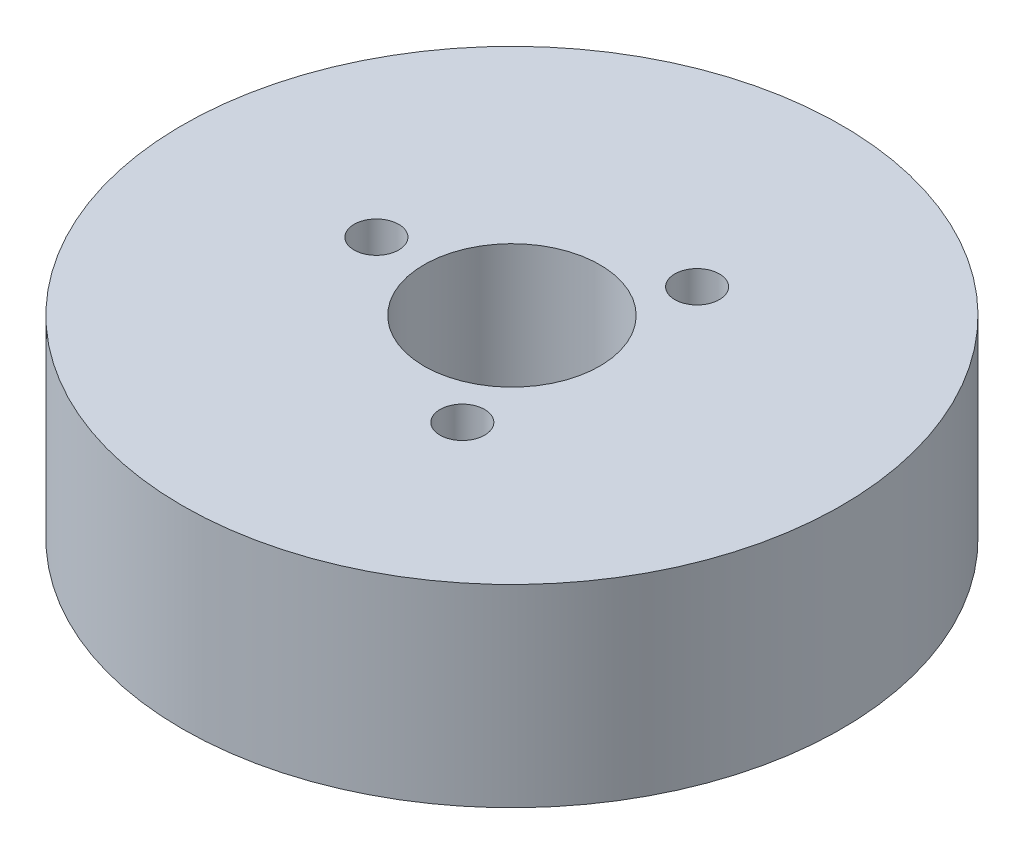
SolidWorks part; units mm, degrees
ref_plane "Front Plane" through (0, 0, 0) normal (0, 0, 1) x (1, 0, 0)
ref_plane "Top Plane" through (0, 0, 0) normal (0, 1, 0) x (1, 0, 0)
ref_plane "Right Plane" through (0, 0, 0) normal (1, 0, 0) x (0, 0, -1)
sketch "Sketch1" plane through (0, 0, 0) normal (0, 1, 0) x (1, 0, 0)
  circle A0 centre (0, 0) radius 37.5
  dimension "FLANGE_OD" = 75
extrude "Boss-Extrude1" add sketch "Sketch1" along normal blind 22
sketch "Sketch2" plane through (0, 0, 0) normal (0, 1, 0) x (1, 0, 0)
  circle A0 centre (0, 0) radius 10
  dimension "BORE_D" = 20
extrude "Cut-Extrude1" cut sketch "Sketch2" along normal through all
sketch "Sketch3" plane through (0, 22, 0) normal (0, 1, 0) x (1, 0, 0)
  circle A0 centre (0, 0) radius 15.4224 construction
  circle A1 centre (-15.4224, 0) radius 2.539
  dimension "BOLT_D" = 5.078
  dimension "BOLT_PCD" = 30.8448
extrude "Cut-Extrude2" cut sketch "Sketch3" against normal blind 18.9793
pattern_circular "CirPattern1" count 3 over 360 about axis through (0, 0, 0) along (0, 1, 0) of "Cut-Extrude2"
